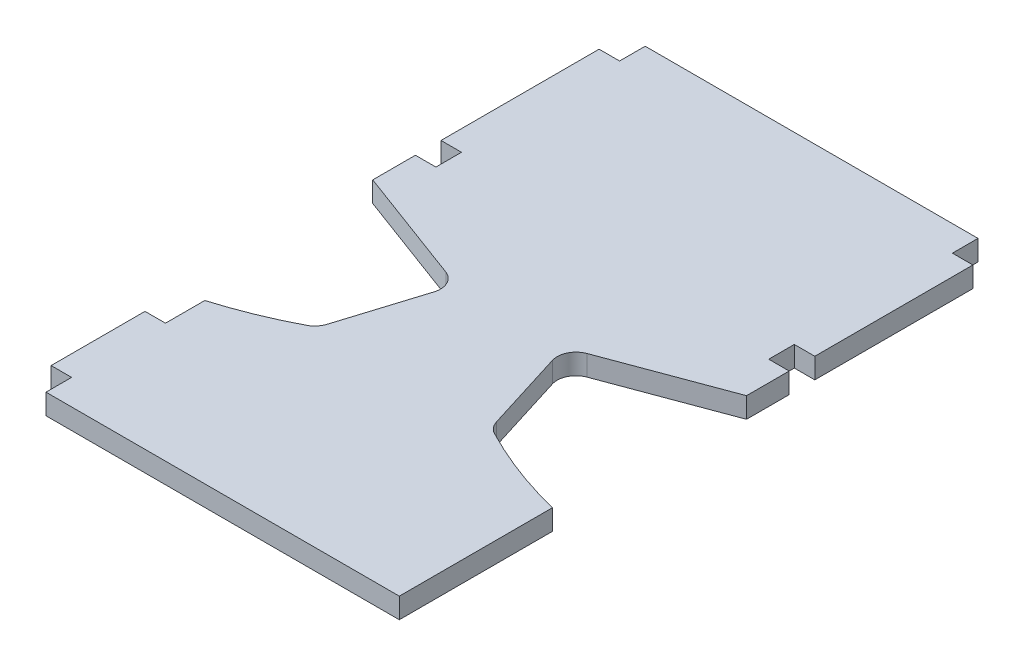
SolidWorks part; units mm, degrees
ref_plane "Front" through (0, 0, 0) normal (0, 0, 1) x (1, 0, 0)
ref_plane "Top" through (0, 0, 0) normal (0, 1, 0) x (1, 0, 0)
ref_plane "Right" through (0, 0, 0) normal (1, 0, 0) x (0, 0, -1)
ref_axis "side-side" through (80.9, 0, 0) along (-1, 0, 0)
ref_axis "up-down" through (0, 50, 0) along (0, -1, 0)
ref_axis "front-back" through (0, 0, -80.9) along (0, 0, 1)
sketch "Sketch1" plane through (0, 0, 0) normal (0, 1, 0) x (1, 0, 0)
  line L0 (0, 45.72) -> (0, 82.7528) construction
  line L1 (-49.53, 45.72) -> (49.53, 45.72)
  line L2 (-55.626, 38.1) -> (-55.626, -8.9519)
  line L3 (-49.53, -132.6173) -> (55.626, -132.6173)
  line L4 (55.626, 38.1) -> (55.626, -8.9519)
  line L5 (0, -50) -> (0, 50) construction
  line L6 (-50, 0) -> (50, 0) construction
  line L7 (-17.632, -49.0369) -> (-25.1877, -73.287) construction
  line L8 (-17.632, -49.0369) -> (-25.1877, -73.287)
  line L9 (-21.0198, -42.1368) -> (-55.626, -29.2719)
  line L10 (-55.626, -97.0573) -> (-55.626, -124.9973)
  line L11 (55.626, -29.2719) -> (21.0198, -42.1368)
  line L12 (17.632, -49.0369) -> (25.1877, -73.287)
  line L13 (55.626, -87.0224) -> (55.626, -132.6173)
  line L14 (55.626, -16.5719) -> (55.626, -29.2719)
  line L15 (-49.53, 38.1) -> (-55.626, 38.1)
  line L16 (-49.53, 38.1) -> (-49.53, 45.72)
  line L17 (-55.626, -16.5719) -> (-55.626, -29.2719)
  line L18 (-21.0198, -42.1368) -> (-55.626, -29.2719) construction
  line L19 (-49.53, -8.9519) -> (-55.626, -8.9519)
  line L20 (-49.53, -8.9519) -> (-49.53, -16.5719)
  line L21 (-49.53, -16.5719) -> (-55.626, -16.5719)
  line L22 (-49.53, -132.6173) -> (-10.668, -132.6173) construction
  line L23 (-49.53, -8.9519) -> (-55.626, -8.9519) construction
  line L25 (55.626, 38.1) -> (49.53, 38.1)
  line L26 (49.53, 45.72) -> (49.53, 38.1)
  line L27 (55.626, -16.5719) -> (49.53, -16.5719)
  line L28 (-49.53, -85.3598) -> (-49.53, -97.0573) construction
  line L29 (55.626, -8.9519) -> (49.53, -8.9519)
  line L30 (49.53, -16.5719) -> (49.53, -8.9519)
  line L31 (-55.626, -97.0573) -> (-49.53, -97.0573) construction
  line L32 (-49.53, -85.3598) -> (-49.53, -97.0573)
  line L33 (-55.626, -97.0573) -> (-49.53, -97.0573)
  line L34 (-49.53, -132.6173) -> (-49.53, -124.9973) construction
  line L35 (-55.626, -124.9973) -> (-49.53, -124.9973) construction
  line L36 (-49.53, -132.6173) -> (-49.53, -124.9973)
  line L37 (-55.626, -124.9973) -> (-49.53, -124.9973)
  arc A0 (-49.53, -85.3598) -> (-27.9391, -76.5796) centre (-85.09, 33.02) ccw construction
  arc A1 (-17.632, -49.0369) -> (-21.0198, -42.1368) centre (-22.967, -47.3746) ccw
  arc A2 (-27.9391, -76.5796) -> (-25.1877, -73.287) centre (-30.5228, -71.6248) ccw
  arc A3 (-27.9391, -76.5796) -> (-49.53, -85.3598) centre (-85.09, 33.02) cw
  arc A4 (21.0198, -42.1368) -> (17.632, -49.0369) centre (22.967, -47.3746) ccw
  arc A5 (25.1877, -73.287) -> (27.9391, -76.5796) centre (30.5228, -71.6248) ccw
  arc A6 (27.9391, -76.5796) -> (55.626, -87.0224) centre (85.09, 33.02) ccw
  dimension "D2" = 11.176
  dimension "D1" = 45.72
  dimension "D3" = 12.7
  dimension "D4" = 111.252
  dimension "D5" = 6.096
  dimension "D6" = 7.62
extrude "Boss-Extrude1" add sketch "Sketch1" along normal mid plane 6.096
